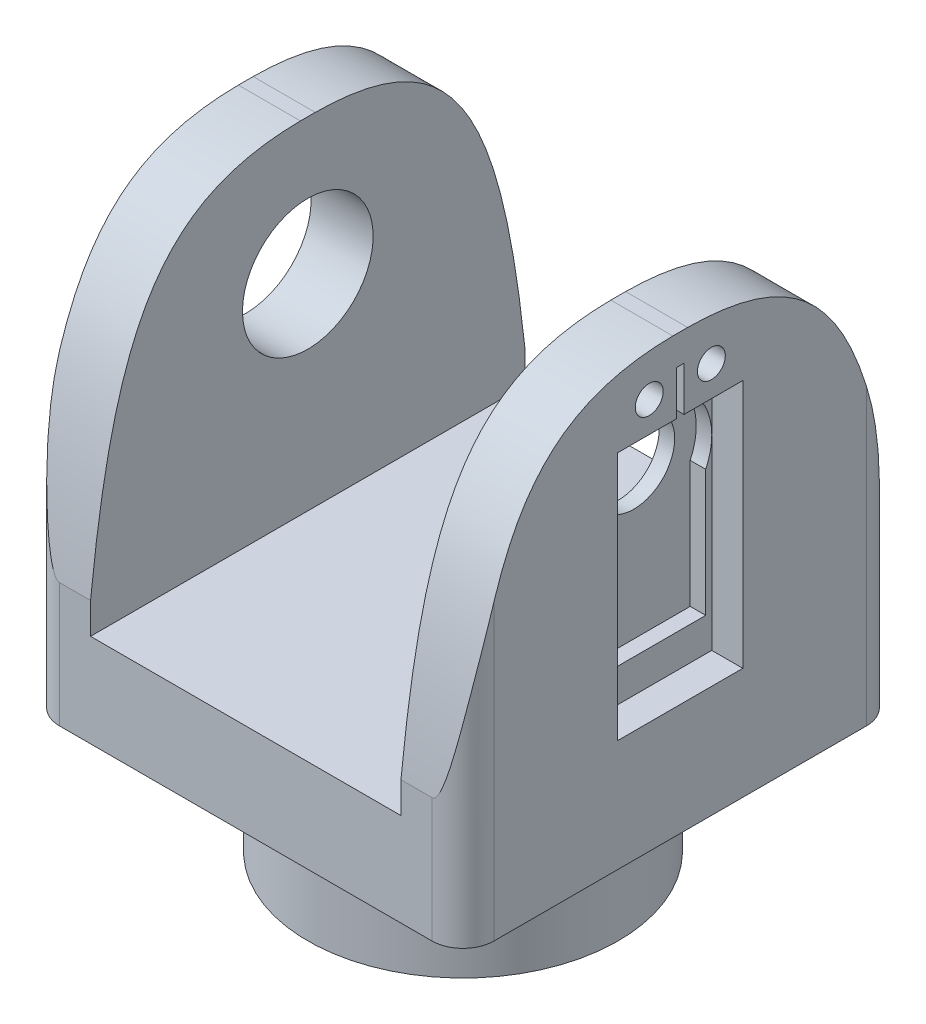
SolidWorks part; units mm, degrees
other "Markup1"
sketch "Sketch11" plane through (35, 90, 35) normal (0.6329, 0.4375, 0.6388) x (0.7444, -0.1168, -0.6574)
ref_plane "Front Plane" through (0, 0, 0) normal (0, 0, 1) x (1, 0, 0)
ref_plane "Top Plane" through (0, 0, 0) normal (0, 1, 0) x (1, 0, 0)
ref_plane "Right Plane" through (0, 0, 0) normal (1, 0, 0) x (0, 0, -1)
sketch "Sketch1" plane through (0, 0, 0) normal (0, 1, 0) x (1, 0, 0)
  line L1 (-35, -35) -> (35, -35)
  line L2 (-35, -35) -> (-35, 35)
  line L3 (-35, 35) -> (35, 35)
  line L4 (35, -35) -> (35, 35)
  line L5 (-35, -35) -> (35, 35) construction
  line L6 (-35, 35) -> (35, -35) construction
  point P0 (0, 0)
  dimension "D1" = 70
  dimension "D2" = 70
extrude "Boss-Extrude1" add sketch "Sketch1" along normal blind 20
sketch "Sketch3" plane through (0, 20, 0) normal (0, 1, 0) x (1, 0, 0)
  line L0 (-35, -35) -> (35, -35) construction
  line L1 (-35, 35) -> (-25, 35)
  line L2 (-35, 35) -> (-35, -35)
  line L3 (-35, -35) -> (-25, -35)
  line L4 (-25, 35) -> (-25, -35)
  line L5 (35, 35) -> (25, 35)
  line L6 (35, 35) -> (35, -35)
  line L7 (35, -35) -> (25, -35)
  line L8 (25, 35) -> (25, -35)
  dimension "D1" = 10
  dimension "D2" = 10
extrude "Boss-Extrude2" add sketch "Sketch3" along normal blind 50
ref_plane "Plane1" through (0, -20, 0) normal (0, -1, 0) x (-1, 0, 0)
sketch "Sketch4" plane through (0, -20, 0) normal (0, -1, 0) x (-1, 0, 0)
  circle A0 centre (0, 0) radius 25
  circle A1 centre (0, 0) radius 20.325
  dimension "D1" = 50
  dimension "D2" = 40.65
extrude "Boss-Extrude3" add sketch "Sketch4" against normal up to surface (20 mm away) up to face at (0, 0, 0)
fillet "Fillet1" radius 10 1 edges at (0, 0, -25)
sketch "Sketch5" plane through (35, 0, 0) normal (1, 0, 0) x (0, 0, -1)
  line L0 (0, 0) -> (0, 18) construction
  line L3 (-10.075, 18) -> (10.075, 18)
  line L4 (-10.075, 18) -> (-10.075, 58.15)
  line L5 (-10.075, 58.15) -> (10.075, 58.15)
  line L6 (10.075, 18) -> (10.075, 58.15)
  line L7 (-10.075, 18) -> (10.075, 58.15) construction
  line L8 (-10.075, 58.15) -> (10.075, 18) construction
  point P5 (0, 38.075)
  dimension "D1" = 20.15
  dimension "D2" = 40.15
  dimension "D3" = 18
extrude "Cut-Extrude1" cut sketch "Sketch5" against normal blind 5 contours L5 L4 L3 | L3 L6 L5 region at (35, 38.075, 0)
sketch "Sketch6" plane through (35, 0, 0) normal (1, 0, 0) x (0, 0, -1)
  line L0 (-35, 70) -> (35, 70) construction
  line L2 (0, 99.9759) -> (0, 81.1621)
  line L3 (-35, 20) -> (35, 20)
  line L4 (-35, 20) -> (-35, 0)
  line L5 (-35, 20) -> (35, 20)
  line L6 (-35, 20) -> (-35, 0)
  line L7 (-35, 0) -> (35, 0)
  line L8 (35, 20) -> (35, 0)
  line L9 (35, 20) -> (35, 0)
  spline S0 degree 3 poles (-35, 20) (-30.9732, 57.5362) (-22.8961, 70.2284) (0, 70) knots 0 0 0 0 0.703349 0.703349 0.703349 0.703349
  spline S1 degree 3 poles (35, 20) (30.9732, 57.5362) (22.8961, 70.2284) (0, 70) knots 0 0 0 0 0.703349 0.703349 0.703349 0.703349
  line M8 (35, 0) -> (35, 70)
  line M9 (35, 70) -> (-35, 70)
  line M10 (-35, 70) -> (-35, 0)
extrude "Cut-Extrude3" cut sketch "Sketch6" against normal blind 140 contours S0 M10 M9 | S1 M8 M9 region at (35, 57.8263, 28.5933) region at (35, 57.8263, -28.5933)
sketch "Sketch8" plane through (30, 0, 0) normal (1, 0, 0) x (0, 0, -1)
  line L0 (0, 18) -> (0, 48.075) construction
  line L5 (0, 0) -> (0, 18) construction
  line L6 (-10.075, 58.15) -> (10.075, 58.15)
  line L7 (-10.075, 58.15) -> (-10.075, 18)
  line L8 (-10.075, 18) -> (10.075, 18)
  line L9 (10.075, 58.15) -> (10.075, 18)
  line L10 (-9.1, 48.075) -> (9.1, 48.075)
  line L11 (-9.1, 48.075) -> (-9.1, 23.375)
  line L12 (-9.1, 23.375) -> (9.1, 23.375)
  line L13 (9.1, 48.075) -> (9.1, 23.375)
  circle A2 centre (0, 48.075) radius 10.075
  circle A4 centre (0, 48.075) radius 6.6
  circle A5 centre (0, 48.075) radius 3.1
  point P8 (0, 58.15)
  point P9 (0, 48.075)
  dimension "D1" = 18.2
  dimension "D2" = 24.7
  dimension "D4" = 13.2
  dimension "D3" = 6.2
  dimension "D5" = 18
extrude "Cut-Extrude4" cut sketch "Sketch8" against normal blind 2.5 contours A4 L10 L13 A2 L11 | A4 L10 L11 A2 L13 | A2 L11 L12 L13 | A5 L10 A4 | A5 | A4 region at (30, 55.024, -6.949) region at (30, 31.5782, 0) region at (30, 45.9131, 8.892) region at (30, 51.2966, 0)
sketch "Sketch9" plane through (0, 20, 0) normal (0, 1, 0) x (1, 0, 0)
  line L1 (-25, 35) -> (25, 35)
  line L2 (-25, 35) -> (-25, -35)
  line L3 (-25, -35) -> (25, -35)
  line L4 (25, 35) -> (25, -35)
extrude "Cut-Extrude5" cut sketch "Sketch9" against normal blind 5
sketch "Sketch10" plane through (0, 0, 0) normal (0, -1, 0) x (1, 0, 0)
  circle A0 centre (0, 0) radius 24
extrude "Cut-Extrude6" [suppressed] cut sketch "Sketch10"
extrude "Cut-Extrude8" cut sketch "Sketch8<4>" against normal blind 6 contours A5 L10 A4 | A5 L10 A4
sketch "Sketch8<4>" plane through (30, 0, 0) normal (1, 0, 0) x (0, 0, -1) same geometry as "Sketch8"
sketch "Sketch12" plane through (35, 0, 0) normal (1, 0, 0) x (0, 0, -1)
  line L0 (0, 65.3) -> (0, 77.3828) construction
  line L1 (-10.075, 58.15) -> (10.075, 58.15)
  line L2 (-10.075, 58.15) -> (-10.075, 65.3)
  line L3 (-10.075, 65.3) -> (10.075, 65.3)
  line L4 (10.075, 58.15) -> (10.075, 65.3)
  line L6 (-0.6, 65.3) -> (0.6, 65.3)
  line L7 (-0.6, 65.3) -> (-0.6, 58.15)
  line L8 (-0.6, 58.15) -> (0.6, 58.15)
  line L9 (0.6, 65.3) -> (0.6, 58.15)
  circle A0 centre (-5.005, 63.05) radius 2.25
  circle A1 centre (5.005, 63.05) radius 2.25
  point P13 (0, 65.3)
  dimension "D3" = 4.5
  dimension "D5" = 1.2
  dimension "D1" = 20.15
  dimension "D2" = 7.15
  dimension "D4" = 5.07
  dimension "D6" = 7.15
extrude "Cut-Extrude9" cut sketch "Sketch12" against normal blind 8 contours A0 | A1 region at (35, 63.05, 5.005) region at (35, 63.05, -5.005)
extrude "Cut-Extrude10" cut sketch "Sketch12<3>" against normal blind 1.6 contours L9 L6 L3 L7 L1 region at (35, 61.725, 0)
sketch "Sketch12<3>" plane through (35, 0, 0) normal (1, 0, 0) x (0, 0, -1) same geometry as "Sketch12"
extrude "Cut-Extrude11" cut sketch "Sketch8<5>" against normal blind 10 contours A5
sketch "Sketch8<5>" plane through (30, 0, 0) normal (1, 0, 0) x (0, 0, -1) same geometry as "Sketch8"
sketch "Sketch13" plane through (-35, 0, 0) normal (-1, 0, 0) x (0, 0, 1)
  circle A0 centre (0, 48.075) radius 10.525
  dimension "D1" = 21.05
extrude "Cut-Extrude12" cut sketch "Sketch13" against normal blind 10
fillet "Fillet2" radius 5 4 edges at (-35, 10, 35) (35, 10, 35) (35, 10, -35) (-35, 10, -35)
